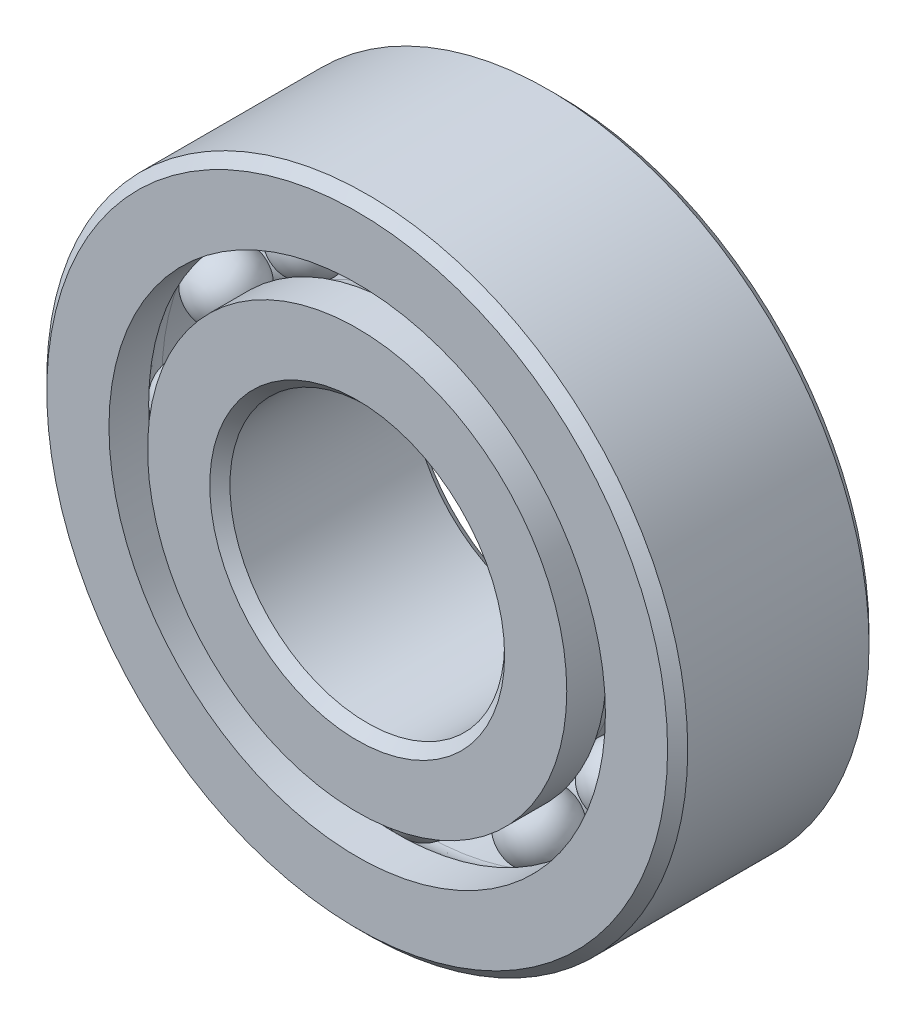
SolidWorks part; units mm, degrees
ref_plane "Front Plane" through (0, 0, 0) normal (0, 0, 1) x (1, 0, 0)
ref_plane "Top Plane" through (0, 0, 0) normal (0, 1, 0) x (1, 0, 0)
ref_plane "Right Plane" through (0, 0, 0) normal (1, 0, 0) x (0, 0, -1)
sketch "Sketch1" plane through (0, 0, 0) normal (1, 0, 0) x (0, 0, -1)
  line L0 (-5.5, 0) -> (5.5, 0) construction
  line L1 (0, 17.5) -> (0, -17.5) construction
  line L2 (4.95, 17.5) -> (-4.95, 17.5)
  line L3 (-4.95, 17.5) -> (-5.5, 16.95)
  line L4 (-5.5, 16.95) -> (-5.5, 13.5549)
  line L5 (-5.5, 13.5549) -> (-1.8333, 13.5549) construction
  line L6 (5.5, 13.5549) -> (1.8333, 13.5549) construction
  line L7 (5.5, 16.95) -> (5.5, 13.5549)
  line L8 (4.95, 17.5) -> (5.5, 16.95)
  line L9 (0, 17.5) -> (0, 12.5) construction
  line L10 (0, 12.5) -> (0, 7.5) construction
  line L11 (-5.5, 13.5549) -> (-3.3327, 13.5549)
  line L12 (5.5, 13.5549) -> (3.3327, 13.5549)
  line L13 (-1.8333, 14.3333) -> (1.8333, 14.3333)
  circle A1 centre (1.8333, 12.5) radius 1.8333 construction
  circle A2 centre (-1.8333, 12.5) radius 1.8333 construction
  arc A3 (1.8333, 14.3333) -> (3.3327, 13.5549) centre (1.8333, 12.5) cw
  arc A4 (-1.8333, 14.3333) -> (-3.3327, 13.5549) centre (-1.8333, 12.5) ccw
  point P14 (0, 7.5)
  dimension "Width" = 11
  dimension "OD" = 35
  dimension "D1" = 45
  dimension "D2" = 0.55
  dimension "Shaft Dia" = 15
  dimension "D3" = 3.6667
  dimension "D4" = 1.0549
revolve "Revolve1" add sketch "Sketch1" angle 360 about L0
sketch "Sketch3" plane through (0, 0, 0) normal (1, 0, 0) x (0, 0, -1)
  line L0 (-5.5, 11.4451) -> (-3.3327, 11.4451)
  line L2 (-5.5, 16.95) -> (-5.5, 13.5549) construction
  line L3 (-5.5, 11.4451) -> (-5.5, 8.05)
  line L4 (-4.95, 17.5) -> (-5.5, 16.95) construction
  line L5 (-5.5, 8.05) -> (-4.95, 7.5)
  line L6 (-4.95, 7.5) -> (4.95, 7.5)
  line L7 (4.95, 17.5) -> (4.95, -17.5) construction
  line L8 (4.95, 7.5) -> (5.5, 8.05)
  line L9 (5.5, -16.95) -> (5.5, 16.95) construction
  line L10 (5.5, 8.05) -> (5.5, 11.4451)
  line L11 (5.5, 11.4451) -> (3.3327, 11.4451)
  line L12 (-1.8333, 10.6667) -> (1.8333, 10.6667)
  line L13 (4.95, 17.5) -> (5.5, 16.95) construction
  line L14 (-1.8333, 14.3333) -> (1.8333, 14.3333) construction
  circle A1 centre (1.8333, 12.5) radius 1.8333 construction
  circle A2 centre (-1.8333, 12.5) radius 1.8333 construction
  arc A3 (1.8333, 10.6667) -> (3.3327, 11.4451) centre (1.8333, 12.5) ccw
  arc A4 (-1.8333, 10.6667) -> (-3.3327, 11.4451) centre (-1.8333, 12.5) cw
revolve "Revolve3" add sketch "Sketch3" angle 360 about L0
sketch "Sketch4" plane through (0, 0, 0) normal (1, 0, 0) x (0, 0, -1)
  line L0 (0, 12.5) -> (3.6667, 12.5)
  circle A0 centre (1.8333, 12.5) radius 1.8333 construction
  arc A1 (0, 12.5) -> (3.6667, 12.5) centre (1.8333, 12.5) cw
  arc A2 (3.3327, 13.5549) -> (1.8333, 14.3333) centre (1.8333, 12.5) ccw construction
revolve "Revolve4" add sketch "Sketch4" angle 360 about L0
mirror "Mirror1" about plane through (0, 0, 0) normal (0, 0, 1) of bodies 104 139
ref_axis "Axis1" through (0, 0, -5.5) along (0, 0, 1)
pattern_circular "CirPattern1" count 12 every 30 about axis through (0, 0, -5.5) along (0, 0, 1) of bodies 140 104 139
sketch "Sketch5" plane through (0, 0, 0) normal (1, 0, 0) x (0, 0, -1)
  line L0 (-5.5, 13.5549) -> (-1.8333, 13.5549) construction
  line L1 (-5.225, 13.5549) -> (-3.6667, 13.5549)
  line L2 (-5.225, 13.5549) -> (-5.225, 11.4451)
  line L3 (-5.225, 11.4451) -> (-3.6667, 11.4451)
  line L4 (-3.6667, 13.5549) -> (-3.6667, 11.4451)
  line L5 (-5.5, 11.4451) -> (-3.3327, 11.4451) construction
  line L6 (5.5, 13.5549) -> (1.8333, 13.5549) construction
  line L7 (5.225, 13.5549) -> (3.6667, 13.5549)
  line L8 (5.225, 13.5549) -> (5.225, 11.4451)
  line L9 (5.225, 11.4451) -> (3.6667, 11.4451)
  line L10 (3.6667, 13.5549) -> (3.6667, 11.4451)
  line L11 (5.5, 11.4451) -> (3.3327, 11.4451) construction
  line L12 (-4.95, 17.5) -> (-5.5, 16.95) construction
  circle A0 centre (-1.8333, 12.5) radius 1.8333 construction
  circle A1 centre (1.8333, 12.5) radius 1.8333 construction
  point P18 (-5.225, 17.225)
revolve "Revolve5" [suppressed] add sketch "Sketch5" angle 360 about L0
equation "\"D2@Sketch1\" = \"Width@Sketch1\"*.05"
equation "\"D3@Sketch1\" = \"Width@Sketch1\"/3"
equation "\"D4@Sketch1\" = (((\"OD@Sketch1\"-\"Width@Sketch1\")/2)/3.25)/3.5"
equation "\"D2@CirPattern1\" = 360/\"Balls@CirPattern1\""
